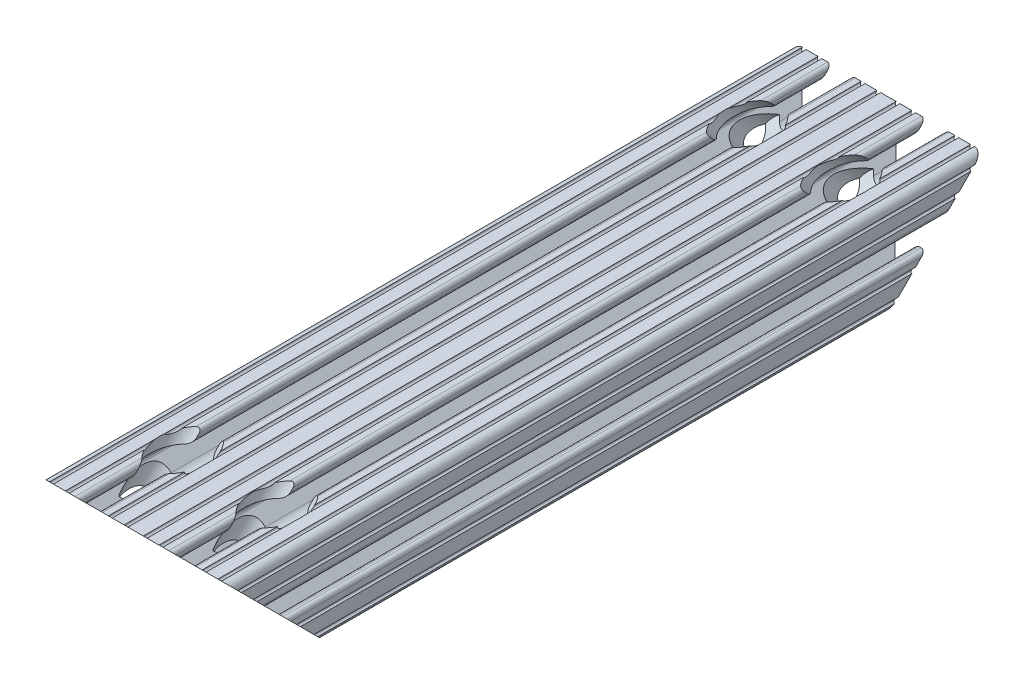
SolidWorks part; units mm, degrees
ref_plane "Front Plane" through (0, 0, 0) normal (0, 0, 1) x (1, 0, 0)
ref_plane "Top Plane" through (0, 0, 0) normal (0, 1, 0) x (1, 0, 0)
ref_plane "Right Plane" through (0, 0, 0) normal (1, 0, 0) x (0, 0, -1)
sketch "Sketch1" plane through (0, 0, 0) normal (0, 0, 1) x (1, 0, 0)
  line L2 (-10.9024, -5.4561) -> (-2.077, -14.2815)
  line L3 (-12.2936, 2.0496) -> (-12.2936, -2.0975)
  line L4 (-2.077, 14.2336) -> (-10.9024, 5.4082)
  line L6 (10.9024, 5.4082) -> (2.077, 14.2336)
  line L7 (12.2936, -2.0975) -> (12.2936, 2.0496)
  line L8 (2.077, -14.2815) -> (10.9024, -5.4561)
  line L9 (8.9158, 13.5105) -> (8.9158, 14.073)
  line L10 (9.8048, 14.962) -> (13.4112, 14.962)
  line L11 (14.986, 16.5368) -> (14.986, 17.4728)
  line L12 (13.4328, 19.026) -> (10.9975, 19.026)
  line L13 (9.4735, 19.026) -> (4.6451, 19.026)
  line L14 (3.1211, 19.026) -> (-3.1211, 19.026)
  line L15 (-4.6451, 19.026) -> (-9.4735, 19.026)
  line L16 (-10.9975, 19.026) -> (-13.4328, 19.026)
  line L17 (-14.986, 17.4728) -> (-14.986, 16.5368)
  line L18 (-13.4112, 14.962) -> (-9.8048, 14.962)
  line L19 (-8.9158, 14.073) -> (-8.9158, 13.5105)
  line L20 (-9.1761, 12.8819) -> (-13.8525, 8.2055)
  line L21 (-17.2111, 6.8143) -> (-20.8889, 6.8143)
  line L22 (-24.2475, 8.2055) -> (-28.9239, 12.8819)
  line L23 (-29.1842, 13.5105) -> (-29.1842, 14.073)
  line L24 (-28.2952, 14.962) -> (-24.6888, 14.962)
  line L25 (-23.114, 16.5368) -> (-23.114, 17.4566)
  line L26 (-24.5589, 19.026) -> (-26.9458, 19.026)
  line L27 (-28.4698, 19.026) -> (-33.2963, 19.026)
  line L28 (-38.1, 14.3513) -> (-38.1, 9.5257)
  line L29 (-38.1, 8.0017) -> (-38.1, 5.6148)
  line L30 (-36.5252, 4.04) -> (-35.6108, 4.04)
  line L31 (-34.036, 5.6148) -> (-34.036, 9.374)
  line L32 (-33.147, 10.263) -> (-32.4207, 10.263)
  line L33 (-31.792, 10.0027) -> (-27.1976, 5.4082)
  line L34 (-25.8064, 2.0496) -> (-25.8064, -2.0975)
  line L35 (-27.1976, -5.4561) -> (-31.792, -10.0506)
  line L36 (-32.4207, -10.311) -> (-33.147, -10.311)
  line L37 (-34.036, -9.422) -> (-34.036, -5.6628)
  line L38 (-35.6108, -4.088) -> (-36.5252, -4.088)
  line L39 (-38.1, -5.6628) -> (-38.1, -8.0497)
  line L40 (-38.1, -9.5737) -> (-38.1, -15.06)
  line L41 (-34.0473, -19.074) -> (-28.4698, -19.074)
  line L42 (-26.9458, -19.074) -> (-24.6888, -19.074)
  line L43 (-23.114, -17.4992) -> (-23.114, -16.5848)
  line L44 (-24.6888, -15.01) -> (-28.448, -15.01)
  line L45 (-29.337, -14.121) -> (-29.337, -13.7111)
  line L46 (-29.0766, -13.0825) -> (-24.2475, -8.2534)
  line L47 (-20.8889, -6.8622) -> (-17.2111, -6.8622)
  line L48 (-13.8525, -8.2534) -> (-9.0234, -13.0825)
  line L49 (-8.763, -13.7111) -> (-8.763, -14.121)
  line L50 (-9.652, -15.01) -> (-13.4112, -15.01)
  line L51 (-14.986, -16.5848) -> (-14.986, -17.4992)
  line L52 (-13.4112, -19.074) -> (-10.9975, -19.074)
  line L53 (-9.4735, -19.074) -> (-4.6451, -19.074)
  line L54 (-3.1211, -19.074) -> (3.1211, -19.074)
  line L55 (4.6451, -19.074) -> (9.4735, -19.074)
  line L56 (10.9975, -19.074) -> (13.4112, -19.074)
  line L57 (14.986, -17.4992) -> (14.986, -16.5848)
  line L58 (13.4112, -15.01) -> (9.652, -15.01)
  line L59 (8.763, -14.121) -> (8.763, -13.7111)
  line L60 (9.0234, -13.0825) -> (13.8525, -8.2534)
  line L61 (17.2111, -6.8622) -> (20.8889, -6.8622)
  line L62 (24.2475, -8.2534) -> (29.0766, -13.0825)
  line L63 (29.337, -13.7111) -> (29.337, -14.121)
  line L64 (28.448, -15.01) -> (24.6888, -15.01)
  line L65 (23.114, -16.5848) -> (23.114, -17.4992)
  line L66 (24.6888, -19.074) -> (26.9458, -19.074)
  line L67 (28.4698, -19.074) -> (34.0473, -19.074)
  line L68 (38.1, -15.06) -> (38.1, -9.5737)
  line L69 (38.1, -8.0497) -> (38.1, -5.6628)
  line L70 (36.5252, -4.088) -> (35.6108, -4.088)
  line L71 (34.036, -5.6628) -> (34.036, -9.422)
  line L72 (33.147, -10.311) -> (32.4207, -10.311)
  line L73 (31.792, -10.0506) -> (27.1976, -5.4561)
  line L74 (25.8064, -2.0975) -> (25.8064, 2.0496)
  line L75 (27.1976, 5.4082) -> (31.792, 10.0027)
  line L76 (32.4207, 10.263) -> (33.147, 10.263)
  line L77 (34.036, 9.374) -> (34.036, 5.6148)
  line L78 (35.6108, 4.04) -> (36.5252, 4.04)
  line L79 (38.1, 5.6148) -> (38.1, 8.0017)
  line L80 (38.1, 9.5257) -> (38.1, 14.3513)
  line L81 (33.2963, 19.026) -> (28.4698, 19.026)
  line L82 (26.9458, 19.026) -> (24.5589, 19.026)
  line L83 (23.114, 17.4566) -> (23.114, 16.5368)
  line L84 (24.6888, 14.962) -> (28.2952, 14.962)
  line L85 (29.1842, 14.073) -> (29.1842, 13.5105)
  line L86 (28.9239, 12.8819) -> (24.2475, 8.2055)
  line L87 (20.8889, 6.8143) -> (17.2111, 6.8143)
  line L88 (13.8525, 8.2055) -> (9.1761, 12.8819)
  circle A0 centre (19.05, -0.024) radius 3.3274
  circle A1 centre (-19.05, -0.024) radius 3.3274
  arc A2 (-2.077, -14.2815) -> (0, -15.1371) centre (-0.0116, -12.216) ccw
  arc A3 (-12.2936, -2.0975) -> (-10.9024, -5.4561) centre (-7.5438, -2.0975) ccw
  arc A4 (-10.9024, 5.4082) -> (-12.2936, 2.0496) centre (-7.5438, 2.0496) ccw
  arc A5 (0, 15.0891) -> (-2.077, 14.2336) centre (-0.0116, 12.1681) ccw
  arc A6 (2.077, 14.2336) -> (0, 15.0891) centre (0.0116, 12.1681) ccw
  arc A7 (12.2936, 2.0496) -> (10.9024, 5.4082) centre (7.5438, 2.0496) ccw
  arc A8 (10.9024, -5.4561) -> (12.2936, -2.0975) centre (7.5438, -2.0975) ccw
  arc A9 (0, -15.1371) -> (2.077, -14.2815) centre (0.0116, -12.216) ccw
  arc A10 (9.8048, 14.962) -> (8.9158, 14.073) centre (9.8048, 14.073) ccw
  arc A11 (13.4112, 14.962) -> (14.986, 16.5368) centre (13.4112, 16.5368) ccw
  arc A12 (14.986, 17.4728) -> (13.4328, 19.026) centre (13.4328, 17.4728) ccw
  arc A13 (9.4735, 19.026) -> (10.9975, 19.026) centre (10.2355, 19.026) ccw
  arc A14 (3.1211, 19.026) -> (4.6451, 19.026) centre (3.8831, 19.026) ccw
  arc A15 (-4.6451, 19.026) -> (-3.1211, 19.026) centre (-3.8831, 19.026) ccw
  arc A16 (-10.9975, 19.026) -> (-9.4735, 19.026) centre (-10.2355, 19.026) ccw
  arc A17 (-13.4328, 19.026) -> (-14.986, 17.4728) centre (-13.4328, 17.4728) ccw
  arc A18 (-14.986, 16.5368) -> (-13.4112, 14.962) centre (-13.4112, 16.5368) ccw
  arc A19 (-8.9158, 14.073) -> (-9.8048, 14.962) centre (-9.8048, 14.073) ccw
  arc A20 (-9.1761, 12.8819) -> (-8.9158, 13.5105) centre (-9.8048, 13.5105) ccw
  arc A21 (-17.2111, 6.8143) -> (-13.8525, 8.2055) centre (-17.2111, 11.5641) ccw
  arc A22 (-24.2475, 8.2055) -> (-20.8889, 6.8143) centre (-20.8889, 11.5641) ccw
  arc A23 (-29.1842, 13.5105) -> (-28.9239, 12.8819) centre (-28.2952, 13.5105) ccw
  arc A24 (-28.2952, 14.962) -> (-29.1842, 14.073) centre (-28.2952, 14.073) ccw
  arc A25 (-24.6888, 14.962) -> (-23.114, 16.5368) centre (-24.6888, 16.5368) ccw
  arc A26 (-23.114, 17.4566) -> (-24.5589, 19.026) centre (-24.6888, 17.4566) ccw
  arc A27 (-28.4698, 19.026) -> (-26.9458, 19.026) centre (-27.7078, 19.026) ccw
  arc A28 (-34.8195, 19.0729) -> (-33.2963, 19.026) centre (-34.0579, 19.0495) ccw
  arc A29 (-34.8195, 19.0729) -> (-38.1376, 15.8743) centre (-34.903, 15.8391) ccw
  arc A30 (-38.1, 14.3513) -> (-38.1376, 15.8743) centre (-38.1, 15.1133) ccw
  arc A31 (-38.1, 8.0017) -> (-38.1, 9.5257) centre (-38.1, 8.7637) ccw
  arc A32 (-38.1, 5.6148) -> (-36.5252, 4.04) centre (-36.5252, 5.6148) ccw
  arc A33 (-35.6108, 4.04) -> (-34.036, 5.6148) centre (-35.6108, 5.6148) ccw
  arc A34 (-33.147, 10.263) -> (-34.036, 9.374) centre (-33.147, 9.374) ccw
  arc A35 (-31.792, 10.0027) -> (-32.4207, 10.263) centre (-32.4207, 9.374) ccw
  arc A36 (-25.8064, 2.0496) -> (-27.1976, 5.4082) centre (-30.5562, 2.0496) ccw
  arc A37 (-27.1976, -5.4561) -> (-25.8064, -2.0975) centre (-30.5562, -2.0975) ccw
  arc A38 (-32.4207, -10.311) -> (-31.792, -10.0506) centre (-32.4207, -9.422) ccw
  arc A39 (-34.036, -9.422) -> (-33.147, -10.311) centre (-33.147, -9.422) ccw
  arc A40 (-34.036, -5.6628) -> (-35.6108, -4.088) centre (-35.6108, -5.6628) ccw
  arc A41 (-36.5252, -4.088) -> (-38.1, -5.6628) centre (-36.5252, -5.6628) ccw
  arc A42 (-38.1, -9.5737) -> (-38.1, -8.0497) centre (-38.1, -8.8117) ccw
  arc A43 (-38.1, -16.584) -> (-38.1, -15.06) centre (-38.1, -15.822) ccw
  arc A44 (-38.1, -16.584) -> (-35.5713, -19.074) centre (-34.9455, -15.9094) ccw
  arc A45 (-34.0473, -19.074) -> (-35.5713, -19.074) centre (-34.8093, -19.074) ccw
  arc A46 (-26.9458, -19.074) -> (-28.4698, -19.074) centre (-27.7078, -19.074) ccw
  arc A47 (-24.6888, -19.074) -> (-23.114, -17.4992) centre (-24.6888, -17.4992) ccw
  arc A48 (-23.114, -16.5848) -> (-24.6888, -15.01) centre (-24.6888, -16.5848) ccw
  arc A49 (-29.337, -14.121) -> (-28.448, -15.01) centre (-28.448, -14.121) ccw
  arc A50 (-29.0766, -13.0825) -> (-29.337, -13.7111) centre (-28.448, -13.7111) ccw
  arc A51 (-20.8889, -6.8622) -> (-24.2475, -8.2534) centre (-20.8889, -11.612) ccw
  arc A52 (-13.8525, -8.2534) -> (-17.2111, -6.8622) centre (-17.2111, -11.612) ccw
  arc A53 (-8.763, -13.7111) -> (-9.0234, -13.0825) centre (-9.652, -13.7111) ccw
  arc A54 (-9.652, -15.01) -> (-8.763, -14.121) centre (-9.652, -14.121) ccw
  arc A55 (-13.4112, -15.01) -> (-14.986, -16.5848) centre (-13.4112, -16.5848) ccw
  arc A56 (-14.986, -17.4992) -> (-13.4112, -19.074) centre (-13.4112, -17.4992) ccw
  arc A57 (-9.4735, -19.074) -> (-10.9975, -19.074) centre (-10.2355, -19.074) ccw
  arc A58 (-3.1211, -19.074) -> (-4.6451, -19.074) centre (-3.8831, -19.074) ccw
  arc A59 (4.6451, -19.074) -> (3.1211, -19.074) centre (3.8831, -19.074) ccw
  arc A60 (10.9975, -19.074) -> (9.4735, -19.074) centre (10.2355, -19.074) ccw
  arc A61 (13.4112, -19.074) -> (14.986, -17.4992) centre (13.4112, -17.4992) ccw
  arc A62 (14.986, -16.5848) -> (13.4112, -15.01) centre (13.4112, -16.5848) ccw
  arc A63 (8.763, -14.121) -> (9.652, -15.01) centre (9.652, -14.121) ccw
  arc A64 (9.0234, -13.0825) -> (8.763, -13.7111) centre (9.652, -13.7111) ccw
  arc A65 (17.2111, -6.8622) -> (13.8525, -8.2534) centre (17.2111, -11.612) ccw
  arc A66 (24.2475, -8.2534) -> (20.8889, -6.8622) centre (20.8889, -11.612) ccw
  arc A67 (29.337, -13.7111) -> (29.0766, -13.0825) centre (28.448, -13.7111) ccw
  arc A68 (28.448, -15.01) -> (29.337, -14.121) centre (28.448, -14.121) ccw
  arc A69 (24.6888, -15.01) -> (23.114, -16.5848) centre (24.6888, -16.5848) ccw
  arc A70 (23.114, -17.4992) -> (24.6888, -19.074) centre (24.6888, -17.4992) ccw
  arc A71 (28.4698, -19.074) -> (26.9458, -19.074) centre (27.7078, -19.074) ccw
  arc A72 (35.5713, -19.074) -> (34.0473, -19.074) centre (34.8093, -19.074) ccw
  arc A73 (35.5713, -19.074) -> (38.1, -16.584) centre (34.9379, -15.9017) ccw
  arc A74 (38.1, -15.06) -> (38.1, -16.584) centre (38.1, -15.822) ccw
  arc A75 (38.1, -8.0497) -> (38.1, -9.5737) centre (38.1, -8.8117) ccw
  arc A76 (38.1, -5.6628) -> (36.5252, -4.088) centre (36.5252, -5.6628) ccw
  arc A77 (35.6108, -4.088) -> (34.036, -5.6628) centre (35.6108, -5.6628) ccw
  arc A78 (33.147, -10.311) -> (34.036, -9.422) centre (33.147, -9.422) ccw
  arc A79 (31.792, -10.0506) -> (32.4207, -10.311) centre (32.4207, -9.422) ccw
  arc A80 (25.8064, -2.0975) -> (27.1976, -5.4561) centre (30.5562, -2.0975) ccw
  arc A81 (27.1976, 5.4082) -> (25.8064, 2.0496) centre (30.5562, 2.0496) ccw
  arc A82 (32.4207, 10.263) -> (31.792, 10.0027) centre (32.4207, 9.374) ccw
  arc A83 (34.036, 9.374) -> (33.147, 10.263) centre (33.147, 9.374) ccw
  arc A84 (34.036, 5.6148) -> (35.6108, 4.04) centre (35.6108, 5.6148) ccw
  arc A85 (36.5252, 4.04) -> (38.1, 5.6148) centre (36.5252, 5.6148) ccw
  arc A86 (38.1, 9.5257) -> (38.1, 8.0017) centre (38.1, 8.7637) ccw
  arc A87 (38.1376, 15.8743) -> (38.1, 14.3513) centre (38.1, 15.1133) ccw
  arc A88 (38.1376, 15.8743) -> (34.8195, 19.0729) centre (34.903, 15.8391) ccw
  arc A89 (33.2963, 19.026) -> (34.8195, 19.0729) centre (34.0579, 19.0495) ccw
  arc A90 (26.9458, 19.026) -> (28.4698, 19.026) centre (27.7078, 19.026) ccw
  arc A91 (24.5589, 19.026) -> (23.114, 17.4566) centre (24.6888, 17.4566) ccw
  arc A92 (23.114, 16.5368) -> (24.6888, 14.962) centre (24.6888, 16.5368) ccw
  arc A93 (29.1842, 14.073) -> (28.2952, 14.962) centre (28.2952, 14.073) ccw
  arc A94 (28.9239, 12.8819) -> (29.1842, 13.5105) centre (28.2952, 13.5105) ccw
  arc A95 (20.8889, 6.8143) -> (24.2475, 8.2055) centre (20.8889, 11.5641) ccw
  arc A96 (13.8525, 8.2055) -> (17.2111, 6.8143) centre (17.2111, 11.5641) ccw
  arc A97 (8.9158, 13.5105) -> (9.1761, 12.8819) centre (9.8048, 13.5105) ccw
extrude "Boss-Extrude1" add sketch "Sketch1" along normal mid plane 304.8
sketch "Sketch2" plane through (0, 0, 0) normal (1, 0, 0) x (0, 0, -1)
  line L0 (-152.4, 19.026) -> (-152.4, -19.074)
  line L1 (-152.4, -19.074) -> (-114.3, -19.074)
  line L2 (-114.3, -19.074) -> (-152.4, 19.026)
  line L3 (0, 0) -> (0, -25.4) construction
  line L5 (114.3, -19.074) -> (152.4, 19.026)
  line L6 (152.4, -19.074) -> (114.3, -19.074)
  line L7 (152.4, 19.026) -> (152.4, -19.074)
  dimension "D1" = 25.4
extrude "Cut-Extrude1" cut sketch "Sketch2" against normal through all and the other way through all
ref_plane "Plane1" through (-19.05, 0, 0) normal (1, 0, 0) x (0, 0, -1)
sketch "Sketch3" plane through (-19.05, 0, 0) normal (1, 0, 0) x (0, 0, -1)
  line L0 (-107.5648, 25.7612) -> (-133.35, -0.024)
  line L1 (-133.35, -0.024) -> (-136.2955, 2.9216)
  line L2 (-136.2955, 2.9216) -> (-131.8054, 7.4117)
  line L3 (-131.8054, 7.4117) -> (-135.5951, 11.2014)
  line L4 (-135.5951, 11.2014) -> (-114.3, 32.4964)
  line L5 (-114.3, 32.4964) -> (-107.5648, 25.7612)
  line L6 (-133.35, -0.024) -> (-136.2955, -2.9695) construction
  line L7 (-114.3, -19.074) -> (-152.4, 19.026) construction
  line L9 (-122.1247, -2.269) -> (-100.8296, 19.026) construction
  line L10 (-136.6774, 3.3034) -> (-130.0226, -3.3514) construction
  dimension "D1" = 8.3312
  dimension "D2" = 19.05
  dimension "D3" = 6.35
revolve "Cut-Revolve1" cut sketch "Sketch3" angle 360 mid plane about L6
mirror "Mirror1" about plane through (0, 0, 0) normal (0, 0, 1) of "Cut-Revolve1"
mirror "Mirror2" about plane through (0, 0, 0) normal (1, 0, 0) of "Mirror1", "Cut-Revolve1"
